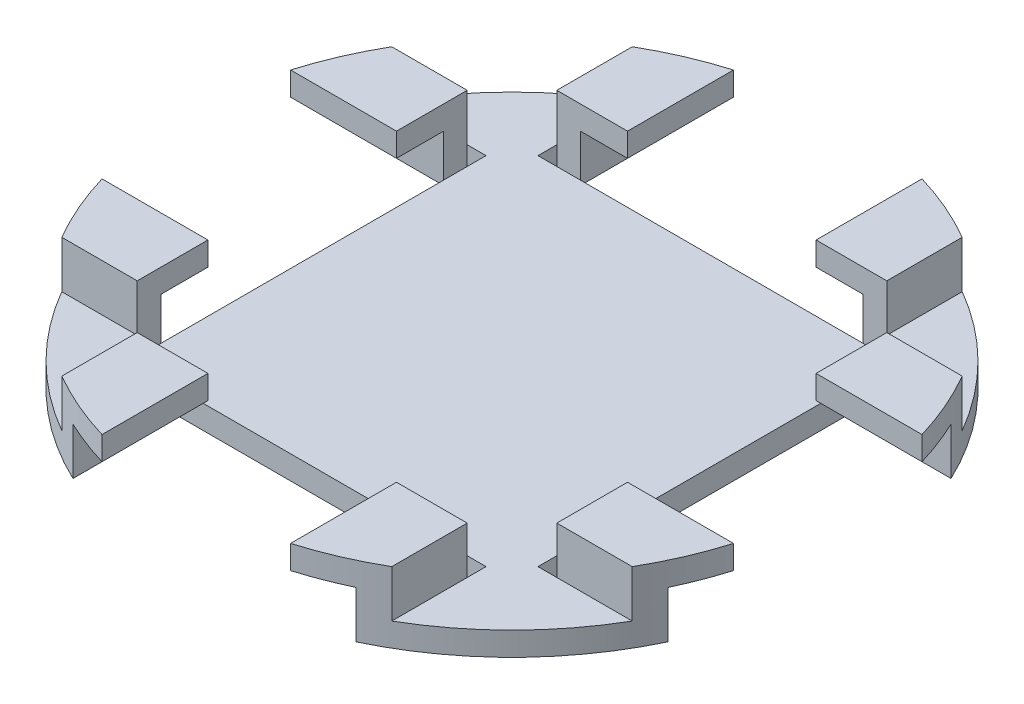
SolidWorks part; units mm, degrees
ref_plane "Front Plane" through (0, 0, 0) normal (0, 0, 1) x (1, 0, 0)
ref_plane "Top Plane" through (0, 0, 0) normal (0, 1, 0) x (1, 0, 0)
ref_plane "Right Plane" through (0, 0, 0) normal (1, 0, 0) x (0, 0, -1)
sketch "Sketch1" plane through (0, 0, 0) normal (0, 1, 0) x (1, 0, 0)
  circle A0 centre (0, 0) radius 88.773
  dimension "D1" = 177.546
extrude "Base" add sketch "Sketch1" along normal blind 6.35
sketch "Sketch2" plane through (0, 6.35, 0) normal (0, 1, 0) x (1, 0, 0)
  line L3 (0, 0) -> (0, -88.773) construction
  line L4 (-44.45, -76.843) -> (-44.45, -51.443)
  line L5 (-44.45, -51.443) -> (0, -51.443)
  line L6 (0, -51.443) -> (44.45, -51.443)
  line L7 (44.45, -51.443) -> (44.45, -76.843)
  arc A1 (44.45, -76.843) -> (0, -88.773) centre (0, 0) cw
  arc A4 (-44.45, -76.843) -> (0, -88.773) centre (0, 0) ccw
  circle A6 centre (0, 0) radius 88.773 construction
  point P2 (-29.0885, -83.8719)
  point P5 (0, -84.7651)
  point P6 (0, 0)
  point P8 (0, 0)
  point P9 (0, -88.0073)
  point P13 (0, 0)
  point P14 (0, -88.773)
  point P15 (0, 0)
  point P16 (0, 0)
  point P17 (0, 0)
  point P20 (-23.1514, -54.8251)
  point P21 (22.2381, -52.8269)
  point P22 (0, -46.1497)
  dimension "D1" = 44.45
  dimension "D2" = 25.4
extrude "Stopper" add sketch "Sketch2" along normal blind 12.7
sketch "Sketch5" plane through (0, 19.05, 0) normal (0, 1, 0) x (1, 0, 0)
  line L3 (0, 0) -> (0, -88.773) construction
  line L4 (-38.1, -80.1813) -> (-38.1, -51.443)
  line L5 (-38.1, -51.443) -> (0, -51.443)
  line L6 (0, -51.443) -> (38.1, -51.443)
  line L7 (38.1, -51.443) -> (38.1, -80.1813)
  line L13 (44.45, -51.443) -> (-44.45, -51.443) construction
  line L14 (-44.45, -51.443) -> (-44.45, -76.843) construction
  arc A1 (38.1, -80.1813) -> (0, -88.773) centre (0, 0) cw
  arc A4 (-38.1, -80.1813) -> (0, -88.773) centre (0, 0) ccw
  arc A7 (-44.45, -76.843) -> (44.45, -76.843) centre (0, 0) ccw construction
  point P2 (0, -78.9057)
  point P3 (0, -92.1339)
  point P5 (0, -88.773)
  point P6 (-33.3916, -82.2536)
  point P15 (0, 0)
  point P16 (0, -79.0015)
  point P17 (0, 0)
  point P20 (0, 0)
  point P21 (0, -79.6475)
  point P22 (0, 0)
  point P24 (0, 0)
  point P25 (0, 0)
  dimension "D1" = 38.1
extrude "Stopper Gap" cut sketch "Sketch5" along direction (0, -1, 0) on the side against the normal through all from offset 6.35 offset against normal yes
sketch "Sketch6" plane through (0, 19.05, 0) normal (0, 1, 0) x (1, 0, 0)
  line L3 (0, 0) -> (0, -88.773) construction
  line L5 (-25.4, -51.443) -> (0, -51.443)
  line L6 (0, -51.443) -> (25.4, -51.443)
  line L10 (44.45, -51.443) -> (-44.45, -51.443) construction
  line L11 (-25.4, -85.0617) -> (-25.4, -56.523)
  line L12 (44.45, -76.843) -> (44.45, -51.443) construction
  line L13 (-44.45, -51.443) -> (-44.45, -76.843) construction
  line L14 (25.4, -85.0617) -> (25.4, -56.523)
  line L15 (-44.45, -51.443) -> (-25.4, -51.443)
  line L16 (-44.45, -51.443) -> (-44.45, -56.523)
  line L17 (-44.45, -56.523) -> (-25.4, -56.523)
  line L19 (25.4, -51.443) -> (44.45, -51.443)
  line L21 (25.4, -56.523) -> (44.45, -56.523)
  line L22 (44.45, -51.443) -> (44.45, -56.523)
  arc A1 (25.4, -85.0617) -> (0, -88.773) centre (0, 0) cw
  arc A4 (-25.4, -85.0617) -> (0, -88.773) centre (0, 0) ccw
  arc A5 (-44.45, -76.843) -> (44.45, -76.843) centre (0, 0) ccw construction
  point P9 (0, -53.729)
  dimension "D1" = 19.05
  dimension "D2" = 5.08
extrude "Overhang cut" cut sketch "Sketch6" against normal blind 26.416
pattern_circular "CirPattern1" count 4 over 360 about axis through (0, 6.35, 0) along (0, 1, 0) of "Overhang cut", "Stopper Gap", "Stopper"
